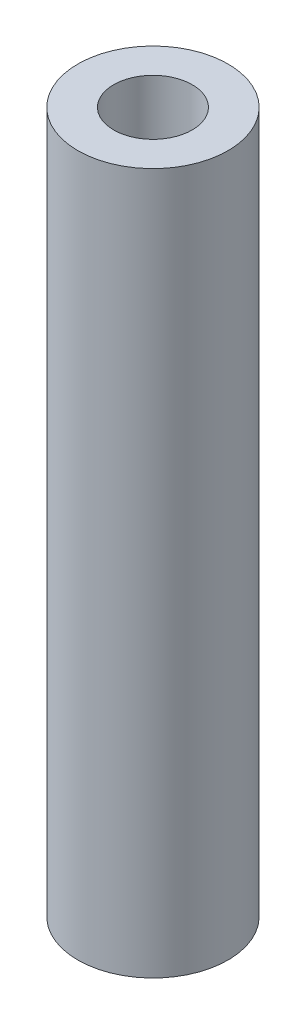
SolidWorks part; units mm, degrees
material "6061-T6 (SS)"
ref_plane "Front Plane" through (0, 0, 0) normal (0, 0, 1) x (1, 0, 0)
ref_plane "Top Plane" through (0, 0, 0) normal (0, 1, 0) x (1, 0, 0)
ref_plane "Right Plane" through (0, 0, 0) normal (1, 0, 0) x (0, 0, -1)
other "Bounding Box"
ref_plane "Default Plane" through (13.8565, 3.175, 6.7999) normal (0, -1, 0) x (-1, 0, 0)
sketch "Sketch1" plane through (0, 0, 0) normal (0, 1, 0) x (1, 0, 0)
  circle A0 centre (0, 0) radius 4.7625
  circle A1 centre (0, 0) radius 2.4892
  dimension "D1" = 9.525
  dimension "D2" = 4.9784
extrude "Boss-Extrude1" add sketch "Sketch1" along normal mid plane 44.45
